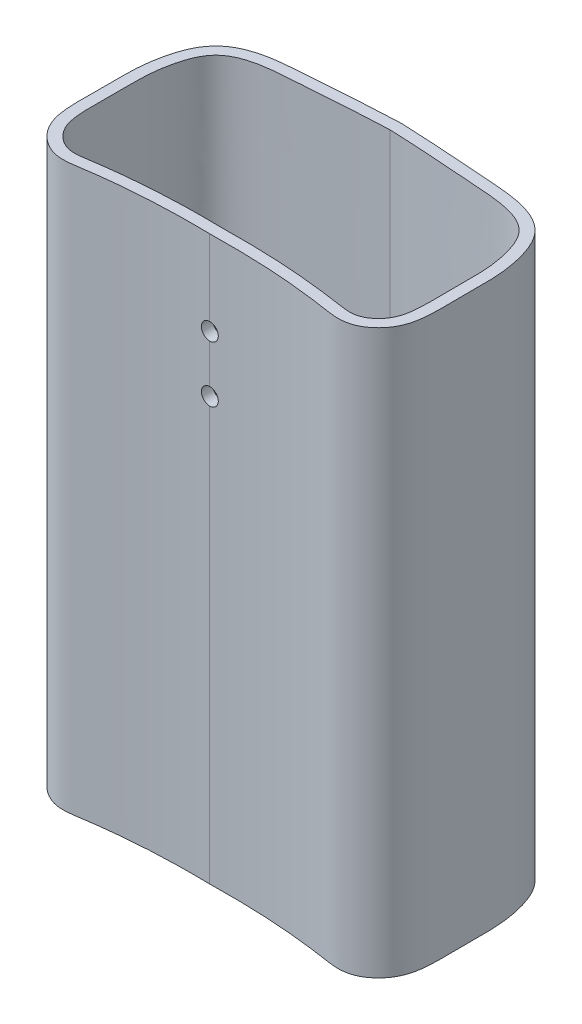
SolidWorks part; units mm, degrees
ref_plane "Ön Düzlem" through (0, 0, 0) normal (0, 0, 1) x (1, 0, 0)
ref_plane "Üst Düzlem" through (0, 0, 0) normal (0, 1, 0) x (1, 0, 0)
ref_plane "Sağ Düzlem" through (0, 0, 0) normal (1, 0, 0) x (0, 0, -1)
sketch "Çizim1" plane through (0, 0, 0) normal (0, 1, 0) x (1, 0, 0)
  line L0 (0, 17.9288) -> (0, -12.0712) construction
  line L1 (0, 0) -> (-30, 0) construction
  line L2 (-108.3091, -42.1463) -> (-63.9653, -42.1463) construction
  spline S0 degree 3 poles (0, 17.9288) (-5.8202, 17.7095) (-13.9034, 17.0426) (-26.8757, 16.196) (-29.5503, 8.9293) (-30.0905, 4.3361) (-29.9407, -0.8874) (-30.1549, -5.7017) (-29.6372, -10.9288) (-26.0312, -14.0818) (-15.7201, -12.3493) (-7.8072, -11.9389) (0, -12.0712) knots 0 0 0 0 0.19846 0.336013 0.394477 0.45973 0.505377 0.582751 0.635933 0.690009 0.731881 1 1 1 1
  spline S1 degree 3 poles (0, 17.9288) (5.8202, 17.7095) (13.9034, 17.0426) (26.8757, 16.196) (29.5503, 8.9293) (30.0905, 4.3361) (29.9407, -0.8874) (30.1549, -5.7017) (29.6372, -10.9288) (26.0312, -14.0818) (15.7201, -12.3493) (7.8072, -11.9389) (0, -12.0712) knots 0 0 0 0 0.19846 0.336013 0.394477 0.45973 0.505377 0.582751 0.635933 0.690009 0.731881 1 1 1 1
  spline S2 degree 1 poles (0, 19.9303) (0, -14.0714) knots 0 0 1 1 construction
  spline S3 degree 1 poles (0, 19.9303) (0, -14.0714) knots 0 0 1 1 construction
  spline S4 degree 3 poles (0, 19.9303) (-0.4569, 19.913) (-1.3788, 19.8761) (-3.1568, 19.7944) (-5.3169, 19.678) (-7.8418, 19.5195) (-11.19, 19.2895) (-14.5919, 19.03) (-18.2872, 18.7842) (-21.2619, 18.4861) (-24.2247, 17.8563) (-26.5803, 16.8232) (-28.2551, 15.5188) (-29.6889, 13.8306) (-30.7777, 11.4296) (-31.5143, 8.5883) (-31.9232, 5.825) (-32.0441, 3.0566) (-31.9879, 0.4286) (-32.0171, -2.0683) (-32.052, -4.7106) (-32.0036, -7.4061) (-31.6486, -10.0115) (-30.6275, -12.1561) (-29.5067, -13.557) (-28.1065, -14.6986) (-26.705, -15.3667) (-25.4582, -15.6359) (-24.2895, -15.7185) (-22.9553, -15.6032) (-21.6185, -15.3841) (-20.348, -15.2005) (-19.0747, -15.0274) (-17.3942, -14.8187) (-15.3102, -14.5944) (-12.8229, -14.3819) (-9.5026, -14.1699) (-6.1385, -14.0592) (-2.6849, -14.0381) (-0.8891, -14.0564) (0, -14.0714) knots -0.000856 -0.000856 -0.000856 -0.000856 0.014788 0.030433 0.061722 0.093011 0.1243 0.186877 0.218166 0.249455 0.280744 0.312033 0.327677 0.343322 0.37461 0.405899 0.437188 0.468477 0.499766 0.531055 0.562344 0.593633 0.624921 0.640566 0.65621 0.671855 0.687499 0.695321 0.703144 0.718788 0.734432 0.750077 0.765721 0.781366 0.812655 0.843944 0.875232 0.93781 0.969099 1.000388 1.000388 1.000388 1.000388
  spline S5 degree 3 poles (0, -14.0714) (0.8891, -14.0564) (2.6849, -14.0381) (6.1385, -14.0592) (9.5026, -14.1699) (12.8229, -14.3819) (15.3102, -14.5944) (17.3942, -14.8187) (19.0747, -15.0274) (20.348, -15.2005) (21.6185, -15.3841) (22.9553, -15.6032) (24.2895, -15.7185) (25.4582, -15.6359) (26.705, -15.3667) (28.1065, -14.6986) (29.5067, -13.557) (30.6275, -12.1561) (31.6486, -10.0115) (32.0036, -7.4061) (32.052, -4.7106) (32.0171, -2.0683) (31.9879, 0.4286) (32.0441, 3.0566) (31.9232, 5.825) (31.5143, 8.5883) (30.7777, 11.4296) (29.6889, 13.8306) (28.2551, 15.5188) (26.5803, 16.8232) (24.2247, 17.8563) (21.2619, 18.4861) (18.2872, 18.7842) (14.5919, 19.03) (11.19, 19.2895) (7.8418, 19.5195) (5.3169, 19.678) (3.1568, 19.7944) (1.3788, 19.8761) (0.4569, 19.913) (0, 19.9303) knots -0.000856 -0.000856 -0.000856 -0.000856 0.030433 0.061722 0.1243 0.155588 0.186877 0.218166 0.233811 0.249455 0.265099 0.280744 0.296388 0.304211 0.312033 0.327677 0.343322 0.358966 0.37461 0.405899 0.437188 0.468477 0.499766 0.531055 0.562344 0.593633 0.624921 0.65621 0.671855 0.687499 0.718788 0.750077 0.781366 0.812655 0.875232 0.906521 0.93781 0.969099 0.984743 1.000388 1.000388 1.000388 1.000388
  dimension "D1" = 30
  dimension "D2" = 30
  dimension "D3" = 2
extrude "Yükseklik-Ekstrüzyon1" add sketch "Çizim1" along normal blind 100
sketch "Çizim2" plane through (0, 100, 0) normal (0, 1, 0) x (1, 0, 0)
  line L0 (0, -14.0714) -> (0, -12.0712)
ref_plane "Düzlem1" through (0, 0, 14.0714) normal (0, 0, -1) x (-1, 0, 0)
sketch "Çizim3" plane through (0, 0, 14.0714) normal (0, 0, -1) x (-1, 0, 0)
  line L0 (0, 100) -> (0, 0) construction
  circle A0 centre (0, 85) radius 1.5
  circle A1 centre (0, 75) radius 1.5
  dimension "D1" = 10
  dimension "D3" = 3
  dimension "D2" = 15
extrude "Kes-Ekstrüzyon1" cut sketch "Çizim3" along normal blind 10
